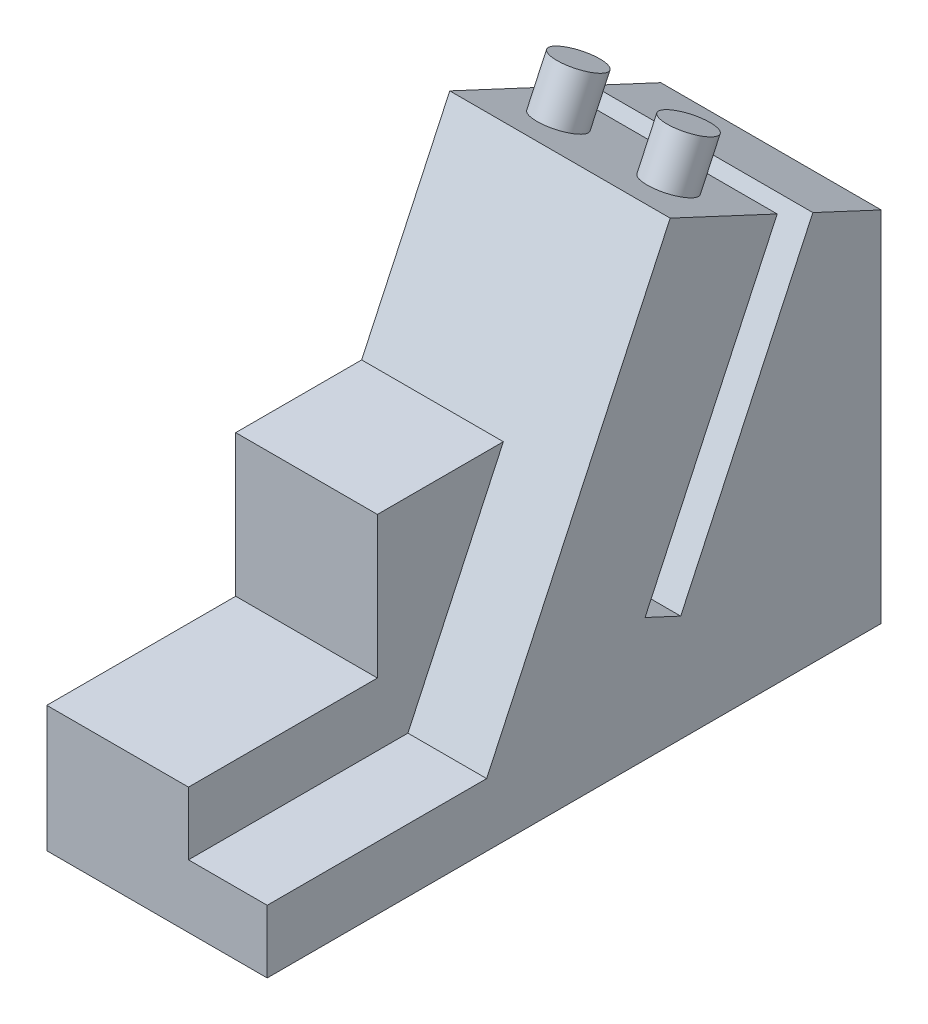
SolidWorks part; units mm, degrees
ref_plane "Front Plane" through (0, 0, 0) normal (0, 0, 1) x (1, 0, 0)
ref_plane "Top Plane" through (0, 0, 0) normal (0, 1, 0) x (1, 0, 0)
ref_plane "Right Plane" through (0, 0, 0) normal (1, 0, 0) x (0, 0, -1)
sketch "Sketch1" plane through (0, 0, 0) normal (0, 1, 0) x (1, 0, 0)
  line L1 (0, 0) -> (28, 0)
  line L2 (0, 0) -> (0, 78)
  line L3 (0, 78) -> (28, 78)
  line L4 (28, 0) -> (28, 78)
  dimension "D1" = 78
  dimension "D2" = 28
extrude "Boss-Extrude1" add sketch "Sketch1" along normal blind 58
sketch "Sketch2" plane through (28, 0, 0) normal (1, 0, 0) x (0, 0, -1)
  line L0 (78, 58) -> (78, 0) construction
  line L1 (0, 0) -> (78, 0)
  line L2 (0, 0) -> (0, 8)
  line L3 (0, 8) -> (27.876, 8)
  line L4 (78, 0) -> (78, 8)
  line L5 (27.876, 8) -> (51.1914, 58)
  line L6 (0, 58) -> (78, 58) construction
  line L7 (51.1914, 58) -> (78, 45.4989)
  line L8 (64.786, 51.6607) -> (69.3175, 49.5476)
  line L9 (64.786, 51.6607) -> (47.9989, 15.6607)
  line L10 (69.3175, 49.5476) -> (52.5305, 13.5476)
  line L11 (47.9989, 15.6607) -> (52.5305, 13.5476)
  line L12 (0, 0) -> (78, 0)
  line L13 (78, 0) -> (78, 58)
  line L14 (78, 58) -> (0, 58)
  line L15 (0, 58) -> (0, 0)
  line L16 (0, 0) -> (78, 0)
  line L17 (78, 0) -> (78, 45.4989)
  line L19 (0, 8) -> (0, 0)
  line L20 (0, 8) -> (0, 16)
  line L21 (0, 58) -> (0, 0) construction
  line L22 (0, 16) -> (24, 16)
  line L23 (24, 16) -> (24, 34)
  line L24 (24, 34) -> (40, 34)
  line M2 (0, 0) -> (78, 0)
  line M3 (78, 0) -> (78, 58)
  line M5 (0, 58) -> (0, 0)
  dimension "D1" = 8
  dimension "D2" = 65
  dimension "D4" = 15
  dimension "D5" = 5
  dimension "D6" = 36
  dimension "D7" = 24
  dimension "D8" = 16
  dimension "D9" = 8
  dimension "D10" = 18
  dimension "D3" = 0
extrude "Cut-Extrude1" cut sketch "Sketch2" against normal through all flip side to cut contours L24 L23 L22 L3 L5 M5 | L11 L9 L7 L5 L3 L10 M5 M2 M3 region at (28, 4, -0.972) region at (28, 12, -0.4771)
extrude "Cut-Extrude2" cut sketch "Sketch2<3>" against normal blind 10 contours L24 L23 L22 L3 L5 M5 region at (28, 12, -0.4771)
sketch "Sketch2<3>" plane through (28, 0, 0) normal (1, 0, 0) x (0, 0, -1) same geometry as "Sketch2"
sketch "Sketch3" plane through (0, 67.2483, -31.3584) normal (0, 0.9063, -0.4226) x (1, 0, 0)
  line L0 (14, 21.8833) -> (14, 32.0905) construction
  line L1 (0, 21.8833) -> (28, 21.8833) construction
  line L2 (0, 21.8833) -> (18, 21.8833) construction
  line L3 (0, 21.8833) -> (0, 36.8833) construction
  circle A0 centre (7, 29.3833) radius 3
  circle A1 centre (21, 29.3833) radius 3
  dimension "D1" = 7.5
  dimension "D2" = 7
  dimension "D3" = 6
extrude "Boss-Extrude2" add sketch "Sketch3" along normal blind 6
